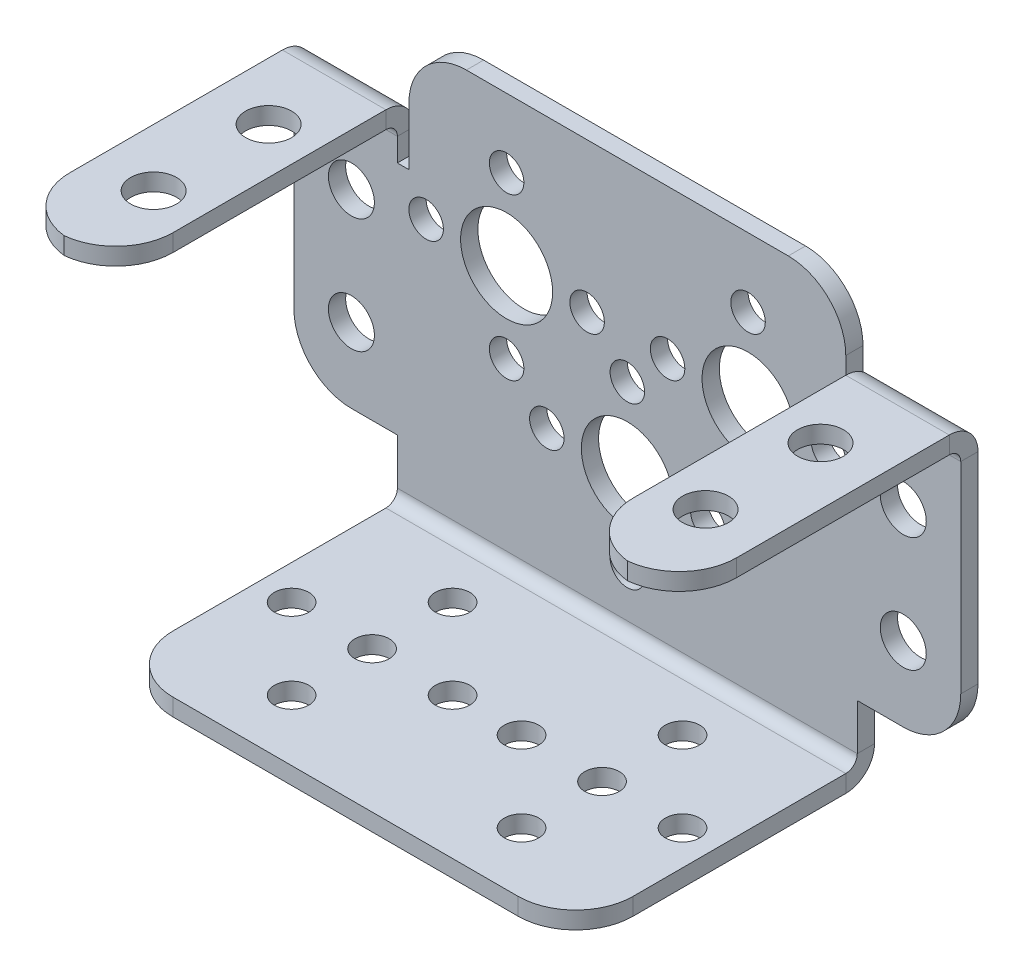
SolidWorks part; units mm, degrees
note: The reader was unsure of these and kept them because the rebuilt part matched: flange length of "Brida de arista3", "Brida de arista4", "Brida de arista5".
ref_plane "Alzado" through (0, 0, 0) normal (0, 0, 1) x (1, 0, 0)
ref_plane "Planta" through (0, 0, 0) normal (0, 1, 0) x (1, 0, 0)
ref_plane "Vista lateral" through (0, 0, 0) normal (1, 0, 0) x (0, 0, -1)
sketch "Croquis1" plane through (0, 0, 0) normal (0, 0, 1) x (1, 0, 0)
  line L0 (20, -17.745) -> (20, -12.745)
  line L1 (-20, -17.745) -> (20, -17.745)
  line L2 (-20, -12.745) -> (-20, -17.745)
  line L3 (19, 17.745) -> (-19, 17.745)
  line L4 (-20, 7.745) -> (-20, 10.755)
  line L7 (20, 10.755) -> (29, 10.755)
  line L9 (-20, 7.745) -> (-19, 7.745)
  line L10 (-19, 17.745) -> (-19, 7.745)
  line L11 (-20, -12.745) -> (-29, -12.745)
  line L12 (20, -12.745) -> (29, -12.745)
  line L13 (20, 7.745) -> (19, 7.745)
  line L14 (19, 17.745) -> (19, 7.745)
  line L15 (-20, 10.755) -> (-29, 10.755)
  line L16 (-29, -12.745) -> (-29, 10.755)
  line L17 (29, 10.755) -> (29, -12.745)
  line L18 (20, 7.745) -> (20, 10.755)
  point P0 (0, 0)
  dimension "D1" = 19
  dimension "D2" = 20
  dimension "D3" = 29
  dimension "D4" = 19
  dimension "D5" = 7.745
  dimension "D6" = 10.755
  dimension "D7" = 17.745
  dimension "D8" = 12.745
  dimension "D9" = 17.745
base flange "Brida base2" sketch "Croquis1" thickness 1.5 reverse thickness direction no parameters "D1"=1
edge flange "Brida de arista3" sketch "Croquis28" flange angle 90 flange length 26 flange position material outside bend radius 1 thickness 1.5 relief rectangular parameters "D6"=10
sketch "Croquis28" plane through (0, -17.745, 0) normal (0, -1, 0) x (1, 0, 0)
  line L2 (-20, 0) -> (-20, 24.5)
  line L3 (-20, 24.5) -> (20, 24.5)
  line L4 (20, 24.5) -> (20, 0)
  line L5 (-20, 0) -> (20, 0) construction
  line L6 (-20, 0) -> (20, 0)
bend "Pliegue de arista3" bend radius 1 bend angle 90 parameters "D5"=1
edge flange "Brida de arista4" sketch "Croquis33" flange angle 90 flange length 26 flange position material outside bend radius 1 thickness 1.5 relief rectangular parameters "D6"=10
sketch "Croquis33" plane through (0, 10.755, 0) normal (0, 1, 0) x (-1, 0, 0)
  line L2 (-29, 0) -> (-29, 24.5)
  line L3 (-29, 24.5) -> (-20, 24.5)
  line L4 (-20, 24.5) -> (-20, 0)
  line L7 (-29, 0) -> (-20, 0) construction
  line L8 (-29, 0) -> (-20, 0)
bend "Pliegue de arista4" bend radius 1 bend angle 90 parameters "D5"=2
edge flange "Brida de arista5" sketch "Croquis36" flange angle 90 flange length 26 flange position material outside bend radius 1 thickness 1.5 relief rectangular parameters "D6"=10
sketch "Croquis36" plane through (0, 10.755, 0) normal (0, 1, 0) x (-1, 0, 0)
  line L0 (20, 0) -> (29, 0) construction
  line L1 (20, 0) -> (29, 0)
  line L2 (20, 0) -> (20, 24.5)
  line L3 (20, 24.5) -> (29, 24.5)
  line L4 (29, 24.5) -> (29, 0)
bend "Pliegue de arista5" bend radius 1 bend angle 90 parameters "D5"=3
fillet "Redondeo1" radius 5 1 edges at (19, 17.745, -0.75)
fillet "Redondeo2" radius 5 1 edges at (-19, 17.745, -0.75)
fillet "Redondeo3" radius 5 1 edges at (-29, -12.745, -0.75)
fillet "Redondeo4" radius 5 1 edges at (29, -12.745, -0.75)
fillet "Redondeo5" radius 5 1 edges at (20, -18.495, 24.5)
fillet "Redondeo6" radius 5 1 edges at (-20, -18.495, 24.5)
fillet "Redondeo7" radius 5 2 edges at (20, 11.505, 24.5) (29, 11.505, 24.5)
fillet "Redondeo8" radius 5 2 edges at (-29, 11.505, 24.5) (-20, 11.505, 24.5)
sketch "Croquis39" plane through (0, 0, 0) normal (0, 0, 1) x (1, 0, 0)
  line L1 (-10.5, 7.745) -> (10.5, 7.745) construction
  circle A0 centre (-10.5, 4.755) radius 4
  circle A1 centre (10.5, 4.755) radius 4
  circle A2 centre (0, -5.745) radius 4
extrude "Cortar-Extruir2" cut sketch "Croquis39" against normal blind 2 contours A2 | A1 | A0 normal cut yes
sketch "Croquis40" plane through (0, 0, 0) normal (0, 0, 1) x (1, 0, 0)
  line L0 (-10.5, 8.755) -> (-10.5, 11.755) construction
  circle A0 centre (-10.5, 4.755) radius 4 construction
  circle A1 centre (-10.5, 11.755) radius 1.5
extrude "Cortar-Extruir3" cut sketch "Croquis40" against normal blind 2 contours A1 normal cut yes
pattern_circular "MatrizC1" count 4 every 90 about axis through (-10.5, 4.755, 0) along (0, 0, 1) of "Cortar-Extruir3"
sketch "Croquis41" plane through (0, 0, 0) normal (0, 0, 1) x (1, 0, 0)
  line L0 (0, -1.745) -> (0, 1.255) construction
  circle A0 centre (0, -5.745) radius 4 construction
  circle A1 centre (0, 1.255) radius 1.5
extrude "Cortar-Extruir4" cut sketch "Croquis41" against normal blind 2 normal cut yes
pattern_circular "MatrizC2" count 4 over 360 about axis through (0, -5.745, 0) along (0, 0, 1) of "Cortar-Extruir4"
sketch "Croquis42" plane through (0, 0, 0) normal (0, 0, 1) x (1, 0, 0)
  circle A1 centre (10.5, 11.755) radius 1.5
extrude "Cortar-Extruir5" cut sketch "Croquis42" against normal blind 2 normal cut yes
pattern_circular "MatrizC3" count 4 over 360 about axis through (10.5, 4.755, 0) along (0, 0, 1) of "Cortar-Extruir5"
sketch "Croquis43" plane through (0, -17.745, 0) normal (0, 1, 0) x (1, 0, 0)
  line L0 (0, -1) -> (0, -24.5) construction
  line L3 (0, -12.75) -> (-20, -12.75) construction
  line L6 (-20, -1) -> (20, -1) construction
  line L7 (15, -24.5) -> (-15, -24.5) construction
  line L8 (-20, -19.5) -> (-20, -1) construction
  line L9 (0, -12.75) -> (20, -12.75) construction
  line L10 (20, -1) -> (20, -19.5) construction
  line L11 (-10, -12.75) -> (-10, -5.75) construction
  circle A0 centre (-10, -12.75) radius 1.5
  circle A1 centre (10, -12.75) radius 1.5
  dimension "D2" = 3
sketch "Croquis46" plane through (0, 0, 0) normal (0, 0, 1) x (1, 0, 0)
  circle A0 centre (24, 3.755) radius 2
  circle A1 centre (24, -6.245) radius 2
  circle A2 centre (-24, 3.755) radius 2
  circle A3 centre (-24, -6.245) radius 2
  dimension "D1" = 2
extrude "Cortar-Extruir9" cut sketch "Croquis46" against normal blind 2 normal cut yes
sketch "Croquis49" plane through (0, 12.255, 0) normal (0, 1, 0) x (1, 0, 0)
  line L0 (-24, -12.1995) -> (-24, -7.1995) construction
  line L4 (-24, -12.1995) -> (24, -12.1995) construction
  circle A2 centre (-24, -7.1995) radius 2
  circle A3 centre (24, -7.1995) radius 2
  circle A4 centre (24, -17.1995) radius 2
  circle A5 centre (-24, -17.1995) radius 2
  dimension "D2" = 2
  dimension "D1" = 5
  dimension "D3" = 2
extrude "Cortar-Extruir10" cut sketch "Croquis49" against normal blind 2 normal cut yes
sketch "Croquis51" plane through (0, -17.745, 0) normal (0, 1, 0) x (1, 0, 0)
  line L0 (-20, -19.5) -> (-20, -1) construction
  line L1 (15, -24.5) -> (-15, -24.5) construction
  circle A1 centre (-10, -12.1995) radius 1.5
  circle A2 centre (10, -12.1995) radius 1.5
  circle A4 centre (17, -12.75) radius 1.5 construction
  dimension "D1" = 3
  dimension "D2" = 10
  dimension "D3" = 30
  dimension "D4" = 12.3005
extrude "Cortar-Extruir11" cut sketch "Croquis51" against normal blind 2 normal cut yes
sketch "Croquis52" plane through (0, -17.745, 0) normal (0, 1, 0) x (1, 0, 0)
  circle A0 centre (-10, -5.1995) radius 1.5
  circle A1 centre (-10, -12.1995) radius 1.5 construction
extrude "Cortar-Extruir12" cut sketch "Croquis52" against normal blind 2 normal cut yes
sketch "Croquis53" plane through (0, -17.745, 0) normal (0, 1, 0) x (1, 0, 0)
  circle A0 centre (10, -5.1995) radius 1.5
  circle A1 centre (-10, -5.1995) radius 1.5 construction
extrude "Cortar-Extruir13" cut sketch "Croquis53" against normal blind 2 normal cut yes
pattern_circular "MatrizC4" count 4 over 360 about axis through (-10, 0, 12.1995) along (0, 1, 0) of "Cortar-Extruir12"
pattern_circular "MatrizC5" count 4 every 90 about axis through (10, 0, 12.1995) along (0, 1, 0) of "Cortar-Extruir13"
sketch "Líneas de pliegue3" plane through (0, 0, 0) normal (0, 1, 0) x (1, 0, 0)
sketch "Cuadro delimitador3" plane through (0, 0, 0) normal (0, 1, 0) x (1, 0, 0)
sheet metal parameters "Chapa metálica3" thickness 1.5 parameters "D1"=1
flat pattern "Chapa desplegada3" [suppressed]
sketch "Líneas de pliegue4" plane through (0, 0, 0) normal (0, 1, 0) x (1, 0, 0)
sketch "Cuadro delimitador4" [suppressed] plane through (0, 0, 0) normal (0, 1, 0) x (1, 0, 0)
sheet metal parameters "Chapa metálica7" thickness 1.5 parameters "D1"=1
flat pattern "Chapa desplegada3" [suppressed]
sketch "Líneas de pliegue4" plane through (0, 0, 0) normal (0, 1, 0) x (1, 0, 0)
sketch "Cuadro delimitador4" [suppressed] plane through (0, 0, 0) normal (0, 1, 0) x (1, 0, 0)
bend of the flat pattern "Aplanar-<Pliegue de arista3>1"
sheet metal parameters "Chapa metálica8" thickness 1.5 parameters "D1"=1
flat pattern "Chapa desplegada3" [suppressed]
sketch "Líneas de pliegue4" plane through (0, 0, 0) normal (0, 1, 0) x (1, 0, 0)
sketch "Cuadro delimitador4" [suppressed] plane through (0, 0, 0) normal (0, 1, 0) x (1, 0, 0)
bend of the flat pattern "Aplanar-<Pliegue de arista3>1"
bend of the flat pattern "Aplanar-<Pliegue de arista4>1"
sheet metal parameters "Chapa metálica9" thickness 1.5 parameters "D1"=1
flat pattern "Chapa desplegada3" [suppressed]
sketch "Líneas de pliegue4" plane through (0, 0, 0) normal (0, 1, 0) x (1, 0, 0)
sketch "Cuadro delimitador4" [suppressed] plane through (0, 0, 0) normal (0, 1, 0) x (1, 0, 0)
bend of the flat pattern "Aplanar-<Pliegue de arista3>1"
bend of the flat pattern "Aplanar-<Pliegue de arista4>1"
bend of the flat pattern "Aplanar-<Pliegue de arista5>1"
sheet metal parameters "Chapa metálica11" thickness 1.5 parameters "D1"=1
flat pattern "Chapa desplegada3" [suppressed]
sketch "Líneas de pliegue4" plane through (0, 0, 0) normal (0, 1, 0) x (1, 0, 0)
sketch "Cuadro delimitador4" [suppressed] plane through (0, 0, 0) normal (0, 1, 0) x (1, 0, 0)
bend of the flat pattern "Aplanar-<Pliegue de arista3>1"
bend of the flat pattern "Aplanar-<Pliegue de arista4>1"
bend of the flat pattern "Aplanar-<Pliegue de arista5>1"
sheet metal parameters "Chapa metálica12" thickness 1.5 parameters "D1"=1
flat pattern "Chapa desplegada3" [suppressed]
sketch "Líneas de pliegue4" plane through (0, 0, 0) normal (0, 1, 0) x (1, 0, 0)
sketch "Cuadro delimitador4" [suppressed] plane through (0, 0, 0) normal (0, 1, 0) x (1, 0, 0)
bend of the flat pattern "Aplanar-<Pliegue de arista3>1"
bend of the flat pattern "Aplanar-<Pliegue de arista4>1"
bend of the flat pattern "Aplanar-<Pliegue de arista5>1"
sheet metal parameters "Chapa metálica13" thickness 1.5 parameters "D1"=1
flat pattern "Chapa desplegada3" [suppressed]
sketch "Líneas de pliegue4" plane through (0, 0, 0) normal (0, 1, 0) x (1, 0, 0)
sketch "Cuadro delimitador4" [suppressed] plane through (0, 0, 0) normal (0, 1, 0) x (1, 0, 0)
bend of the flat pattern "Aplanar-<Pliegue de arista3>1"
bend of the flat pattern "Aplanar-<Pliegue de arista4>1"
bend of the flat pattern "Aplanar-<Pliegue de arista5>1"
sheet metal parameters "Chapa metálica14" thickness 1.5 parameters "D1"=1
flat pattern "Chapa desplegada3" [suppressed]
sketch "Líneas de pliegue4" plane through (0, 0, 0) normal (0, 1, 0) x (1, 0, 0)
sketch "Cuadro delimitador4" [suppressed] plane through (0, 0, 0) normal (0, 1, 0) x (1, 0, 0)
bend of the flat pattern "Aplanar-<Pliegue de arista3>1"
bend of the flat pattern "Aplanar-<Pliegue de arista4>1"
bend of the flat pattern "Aplanar-<Pliegue de arista5>1"
sheet metal parameters "Chapa metálica15" thickness 1.5 parameters "D1"=1
flat pattern "Chapa desplegada3" [suppressed]
sketch "Líneas de pliegue4" plane through (0, 0, 0) normal (0, 1, 0) x (1, 0, 0)
sketch "Cuadro delimitador4" [suppressed] plane through (0, 0, 0) normal (0, 1, 0) x (1, 0, 0)
bend of the flat pattern "Aplanar-<Pliegue de arista3>1"
bend of the flat pattern "Aplanar-<Pliegue de arista4>1"
bend of the flat pattern "Aplanar-<Pliegue de arista5>1"
sheet metal parameters "Chapa metálica16" thickness 1.5 parameters "D1"=1
flat pattern "Chapa desplegada3" [suppressed]
sketch "Líneas de pliegue4" plane through (0, 0, 0) normal (0, 1, 0) x (1, 0, 0)
sketch "Cuadro delimitador4" [suppressed] plane through (0, 0, 0) normal (0, 1, 0) x (1, 0, 0)
bend of the flat pattern "Aplanar-<Pliegue de arista3>1"
bend of the flat pattern "Aplanar-<Pliegue de arista4>1"
bend of the flat pattern "Aplanar-<Pliegue de arista5>1"
sheet metal parameters "Chapa metálica17" thickness 1.5 parameters "D1"=1
flat pattern "Chapa desplegada3" [suppressed]
sketch "Líneas de pliegue4" plane through (0, 0, 0) normal (0, 1, 0) x (1, 0, 0)
sketch "Cuadro delimitador4" [suppressed] plane through (0, 0, 0) normal (0, 1, 0) x (1, 0, 0)
bend of the flat pattern "Aplanar-<Pliegue de arista3>1"
bend of the flat pattern "Aplanar-<Pliegue de arista4>1"
bend of the flat pattern "Aplanar-<Pliegue de arista5>1"
sheet metal parameters "Chapa metálica23" thickness 1.5 parameters "D1"=1
flat pattern "Chapa desplegada3" [suppressed]
sketch "Líneas de pliegue4" plane through (0, 0, 0) normal (0, 1, 0) x (1, 0, 0)
sketch "Cuadro delimitador4" [suppressed] plane through (0, 0, 0) normal (0, 1, 0) x (1, 0, 0)
bend of the flat pattern "Aplanar-<Pliegue de arista3>1"
bend of the flat pattern "Aplanar-<Pliegue de arista4>1"
bend of the flat pattern "Aplanar-<Pliegue de arista5>1"
sheet metal parameters "Chapa metálica24" thickness 1.5 parameters "D1"=1
flat pattern "Chapa desplegada3"
sketch "Líneas de pliegue4" plane through (0, 0, 0) normal (0, 0, 1) x (1, 0, 0)
  line L0 (-20, 10.776) -> (-29, 10.776) construction
  line L1 (29, 10.776) -> (20, 10.776) construction
  line L2 (-20, -17.766) -> (20, -17.766) construction
  line L3 (-20, 10.776) -> (-29, 10.776) construction
  line L4 (29, 10.776) -> (20, 10.776) construction
  line L5 (-20, -17.766) -> (20, -17.766) construction
sketch3d "Cuadro delimitador4" [suppressed]
  line L0 (29, -42.287, 0) -> (29, 35.272, 0) construction
  line L1 (-29, -42.287, 0) -> (-29, 35.272, 0) construction
  line L2 (29, -42.287, 0) -> (-29, -42.287, 0) construction
  line L3 (29, 35.272, 0) -> (-29, 35.272, 0) construction
bend of the flat pattern "Aplanar-<Pliegue de arista3>1"
bend of the flat pattern "Aplanar-<Pliegue de arista4>1"
bend of the flat pattern "Aplanar-<Pliegue de arista5>1"
sheet metal parameters "Chapa metálica25" thickness 1.5 parameters "D1"=1
flat pattern "Chapa desplegada3"
sketch "Líneas de pliegue4" plane through (0, 0, 0) normal (0, 0, 1) x (1, 0, 0)
  line L0 (-20, 10.776) -> (-29, 10.776) construction
  line L1 (29, 10.776) -> (20, 10.776) construction
  line L2 (-20, -17.766) -> (20, -17.766) construction
  line L3 (-20, 10.776) -> (-29, 10.776) construction
  line L4 (29, 10.776) -> (20, 10.776) construction
  line L5 (-20, -17.766) -> (20, -17.766) construction
sketch3d "Cuadro delimitador4" [suppressed]
  line L0 (29, -42.287, 0) -> (29, 35.272, 0) construction
  line L1 (-29, -42.287, 0) -> (-29, 35.272, 0) construction
  line L2 (29, -42.287, 0) -> (-29, -42.287, 0) construction
  line L3 (29, 35.272, 0) -> (-29, 35.272, 0) construction
bend of the flat pattern "Aplanar-<Pliegue de arista3>1"
bend of the flat pattern "Aplanar-<Pliegue de arista4>1"
bend of the flat pattern "Aplanar-<Pliegue de arista5>1"
sheet metal parameters "Chapa metálica26" thickness 1.5 parameters "D1"=1
flat pattern "Chapa desplegada3"
sketch "Líneas de pliegue4" plane through (0, 0, 0) normal (0, 0, 1) x (1, 0, 0)
  line L0 (-20, 10.776) -> (-29, 10.776) construction
  line L1 (29, 10.776) -> (20, 10.776) construction
  line L2 (-20, -17.766) -> (20, -17.766) construction
  line L3 (-20, 10.776) -> (-29, 10.776) construction
  line L4 (29, 10.776) -> (20, 10.776) construction
  line L5 (-20, -17.766) -> (20, -17.766) construction
sketch3d "Cuadro delimitador4" [suppressed]
  line L0 (29, -42.287, 0) -> (29, 35.272, 0) construction
  line L1 (-29, -42.287, 0) -> (-29, 35.272, 0) construction
  line L2 (29, -42.287, 0) -> (-29, -42.287, 0) construction
  line L3 (29, 35.272, 0) -> (-29, 35.272, 0) construction
bend of the flat pattern "Aplanar-<Pliegue de arista3>1"
bend of the flat pattern "Aplanar-<Pliegue de arista4>1"
bend of the flat pattern "Aplanar-<Pliegue de arista5>1"
sheet metal parameters "Chapa metálica27" thickness 1.5 parameters "D1"=1
flat pattern "Chapa desplegada3"
sketch "Líneas de pliegue4" plane through (0, 0, 0) normal (0, 0, 1) x (1, 0, 0)
  line L0 (-20, 10.776) -> (-29, 10.776) construction
  line L1 (29, 10.776) -> (20, 10.776) construction
  line L2 (-20, -17.766) -> (20, -17.766) construction
  line L3 (-20, 10.776) -> (-29, 10.776) construction
  line L4 (29, 10.776) -> (20, 10.776) construction
  line L5 (-20, -17.766) -> (20, -17.766) construction
sketch3d "Cuadro delimitador4" [suppressed]
  line L0 (29, -42.287, 0) -> (29, 35.272, 0) construction
  line L1 (-29, -42.287, 0) -> (-29, 35.272, 0) construction
  line L2 (29, -42.287, 0) -> (-29, -42.287, 0) construction
  line L3 (29, 35.272, 0) -> (-29, 35.272, 0) construction
bend of the flat pattern "Aplanar-<Pliegue de arista3>1"
bend of the flat pattern "Aplanar-<Pliegue de arista4>1"
bend of the flat pattern "Aplanar-<Pliegue de arista5>1"
sheet metal parameters "Chapa metálica28" thickness 1.5 parameters "D1"=1
flat pattern "Chapa desplegada3"
sketch "Líneas de pliegue4" plane through (0, 0, 0) normal (0, 0, 1) x (1, 0, 0)
  line L0 (-20, 10.776) -> (-29, 10.776) construction
  line L1 (29, 10.776) -> (20, 10.776) construction
  line L2 (-20, -17.766) -> (20, -17.766) construction
  line L3 (-20, 10.776) -> (-29, 10.776) construction
  line L4 (29, 10.776) -> (20, 10.776) construction
  line L5 (-20, -17.766) -> (20, -17.766) construction
sketch3d "Cuadro delimitador4" [suppressed]
  line L0 (29, -42.287, 0) -> (29, 35.272, 0) construction
  line L1 (-29, -42.287, 0) -> (-29, 35.272, 0) construction
  line L2 (29, -42.287, 0) -> (-29, -42.287, 0) construction
  line L3 (29, 35.272, 0) -> (-29, 35.272, 0) construction
bend of the flat pattern "Aplanar-<Pliegue de arista3>1"
bend of the flat pattern "Aplanar-<Pliegue de arista4>1"
bend of the flat pattern "Aplanar-<Pliegue de arista5>1"
sheet metal parameters "Chapa metálica29" thickness 1.5 parameters "D1"=1
flat pattern "Chapa desplegada3"
sketch "Líneas de pliegue4" plane through (0, 0, 0) normal (0, 0, 1) x (1, 0, 0)
  line L0 (-20, 10.776) -> (-29, 10.776) construction
  line L1 (29, 10.776) -> (20, 10.776) construction
  line L2 (-20, -17.766) -> (20, -17.766) construction
  line L3 (-20, 10.776) -> (-29, 10.776) construction
  line L4 (29, 10.776) -> (20, 10.776) construction
  line L5 (-20, -17.766) -> (20, -17.766) construction
sketch3d "Cuadro delimitador4" [suppressed]
  line L0 (29, -42.287, 0) -> (29, 35.272, 0) construction
  line L1 (-29, -42.287, 0) -> (-29, 35.272, 0) construction
  line L2 (29, -42.287, 0) -> (-29, -42.287, 0) construction
  line L3 (29, 35.272, 0) -> (-29, 35.272, 0) construction
bend of the flat pattern "Aplanar-<Pliegue de arista3>1"
bend of the flat pattern "Aplanar-<Pliegue de arista4>1"
bend of the flat pattern "Aplanar-<Pliegue de arista5>1"
